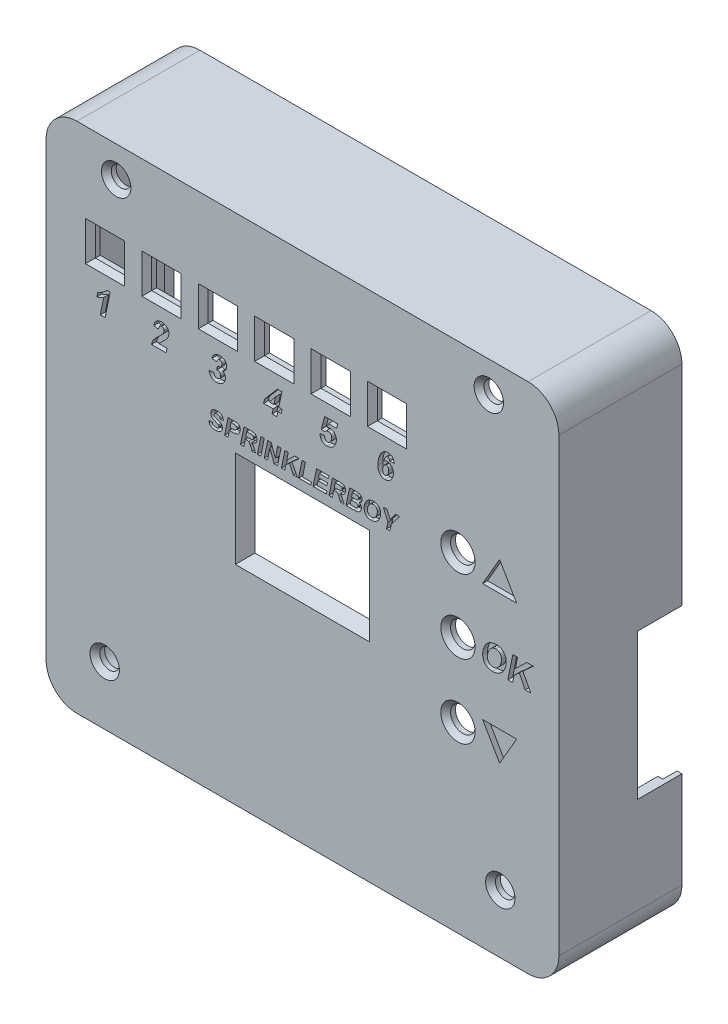
SolidWorks part; units mm, degrees
ref_plane "Front Plane" through (0, 0, 0) normal (0, 0, 1) x (1, 0, 0)
ref_plane "Top Plane" through (0, 0, 0) normal (0, 1, 0) x (1, 0, 0)
ref_plane "Right Plane" through (0, 0, 0) normal (1, 0, 0) x (0, 0, -1)
sketch "Sketch1" plane through (0, 0, 106.9354) normal (0, 0, 1) x (1, 0, 0)
  line L0 (-17.9008, 110.3032) -> (74.0994, 110.3032) construction
  line L1 (80.3867, 104.0159) -> (80.3867, 61.3601) construction
  line L2 (-24.1881, 12.0157) -> (-24.1881, 104.0159) construction
  line L3 (-13.5528, 5.7284) -> (-17.9008, 5.7284) construction
  line L6 (-17.9008, 110.3032) -> (74.0994, 110.3032)
  line L7 (80.3867, 104.0159) -> (80.3867, 61.3601)
  line L8 (-24.1881, 12.0157) -> (-24.1881, 104.0159)
  line L9 (-13.5528, 5.7284) -> (-17.9008, 5.7284)
  line L13 (80.3867, 31.6547) -> (80.3867, 12.0157) construction
  line L14 (80.3867, 31.6547) -> (80.3867, 12.0157)
  line L15 (-13.5528, 5.7284) -> (69.2377, 5.7284) construction
  line L16 (-13.5528, 5.7284) -> (69.2377, 5.7284)
  line L17 (80.3867, 31.6547) -> (80.3867, 61.3601) construction
  line L18 (80.3867, 31.6547) -> (80.3867, 61.3601)
  line L19 (74.0994, 5.7284) -> (69.2377, 5.7284) construction
  line L20 (74.0994, 5.7284) -> (69.2377, 5.7284)
  arc A0 (80.3867, 104.0159) -> (74.0994, 110.3032) centre (74.0994, 104.0159) ccw construction
  arc A1 (-17.9008, 110.3032) -> (-24.1881, 104.0159) centre (-17.9008, 104.0159) ccw construction
  arc A2 (-24.1881, 12.0157) -> (-17.9008, 5.7284) centre (-17.9008, 12.0157) ccw construction
  arc A4 (80.3867, 104.0159) -> (74.0994, 110.3032) centre (74.0994, 104.0159) ccw
  arc A5 (-17.9008, 110.3032) -> (-24.1881, 104.0159) centre (-17.9008, 104.0159) ccw
  arc A6 (-24.1881, 12.0157) -> (-17.9008, 5.7284) centre (-17.9008, 12.0157) ccw
  arc A8 (74.0994, 5.7284) -> (80.3867, 12.0157) centre (74.0994, 12.0157) ccw construction
  arc A9 (74.0994, 5.7284) -> (80.3867, 12.0157) centre (74.0994, 12.0157) ccw
extrude "Boss-Extrude1" add sketch "Sketch1" along normal blind 2
sketch "Sketch3" plane through (0, 0, 106.9354) normal (0, 0, -1) x (-1, 0, 0)
  line L13 (24.1881, 104.0159) -> (24.1881, 12.0157) construction
  line L14 (17.9008, 5.7284) -> (-74.0994, 5.7284) construction
  line L15 (-80.3867, 12.0157) -> (-80.3867, 104.0159) construction
  line L16 (-74.0994, 110.3032) -> (17.9008, 110.3032) construction
  line L17 (24.1881, 104.0159) -> (24.1881, 12.0157)
  line L18 (17.9008, 5.7284) -> (-74.0994, 5.7284)
  line L19 (-80.3867, 12.0157) -> (-80.3867, 104.0159)
  line L20 (-74.0994, 110.3032) -> (17.9008, 110.3032)
  line L21 (-74.0994, 108.3032) -> (17.9008, 108.3032)
  line L22 (22.1881, 104.0159) -> (22.1881, 12.0157)
  line L23 (17.9008, 7.7284) -> (-74.0994, 7.7284)
  line L24 (-78.3867, 12.0157) -> (-78.3867, 104.0159)
  arc A12 (24.1881, 104.0159) -> (17.9008, 110.3032) centre (17.9008, 104.0159) ccw construction
  arc A13 (17.9008, 5.7284) -> (24.1881, 12.0157) centre (17.9008, 12.0157) ccw construction
  arc A14 (-80.3867, 12.0157) -> (-74.0994, 5.7284) centre (-74.0994, 12.0157) ccw construction
  arc A15 (-74.0994, 110.3032) -> (-80.3867, 104.0159) centre (-74.0994, 104.0159) ccw construction
  arc A16 (24.1881, 104.0159) -> (17.9008, 110.3032) centre (17.9008, 104.0159) ccw
  arc A17 (17.9008, 5.7284) -> (24.1881, 12.0157) centre (17.9008, 12.0157) ccw
  arc A18 (-80.3867, 12.0157) -> (-74.0994, 5.7284) centre (-74.0994, 12.0157) ccw
  arc A19 (-74.0994, 110.3032) -> (-80.3867, 104.0159) centre (-74.0994, 104.0159) ccw
  arc A20 (22.1881, 104.0159) -> (17.9008, 108.3032) centre (17.9008, 104.0159) ccw
  arc A21 (17.9008, 7.7284) -> (22.1881, 12.0157) centre (17.9008, 12.0157) ccw
  arc A22 (-78.3867, 12.0157) -> (-74.0994, 7.7284) centre (-74.0994, 12.0157) ccw
  arc A23 (-74.0994, 108.3032) -> (-78.3867, 104.0159) centre (-74.0994, 104.0159) ccw
  dimension "D1" = 2
extrude "Boss-Extrude2" add sketch "Sketch3" along normal up to surface (20.1862 mm away)
sketch "Sketch4" plane through (0, 0, 108.9354) normal (0, 0, 1) x (1, 0, 0)
  circle A0 centre (-9.9008, 104.0159) radius 2
  circle A1 centre (66.0994, 104.0159) radius 2
  circle A2 centre (68.4425, 17.6725) radius 2
  circle A3 centre (-12.244, 17.6725) radius 1.998
extrude "Cut-Extrude1" cut sketch "Sketch4" against normal up to next
sketch "Sketch5" plane through (0, 0, 108.9354) normal (0, 0, 1) x (1, 0, 0)
  line L0 (39.2941, 65.3848) -> (16.9045, 65.3848) construction
  line L1 (16.9045, 65.3848) -> (39.2941, 65.3848)
  line L2 (16.9045, 65.3848) -> (16.9045, 50.6848)
  line L3 (16.9045, 50.6848) -> (39.2941, 50.6848)
  line L4 (39.2941, 65.3848) -> (39.2941, 50.6848)
  line L5 (16.9045, 65.3848) -> (16.9045, 50.6848) construction
  line L6 (16.9045, 50.6848) -> (39.2941, 50.6848) construction
extrude "Cut-Extrude2" cut sketch "Sketch5" against normal up to next
chamfer "Chamfer1" distance 2.5 angle 45 4 edges at (28.0993, 50.6848, 108.9354) (39.2941, 58.0348, 108.9354) (16.9045, 58.0348, 108.9354) (28.0993, 65.3848, 108.9354)
sketch "Sketch7" plane through (80.3867, 0, 0) normal (1, 0, 0) x (0, 0, -1)
  line L0 (-92.9354, 104.0159) -> (-92.9354, 12.0157) construction
  line L1 (-92.9354, 31.6547) -> (-75.9354, 31.6547)
  line L2 (-92.9354, 31.6547) -> (-92.9354, 61.3601)
  line L3 (-92.9354, 61.3601) -> (-75.9354, 61.3601)
  line L4 (-75.9354, 31.6547) -> (-75.9354, 61.3601)
  line L5 (-83.5354, 31.7547) -> (-91.3354, 31.7547) construction
  line L6 (-83.5354, 61.2601) -> (-91.3354, 61.2601) construction
  dimension "D1" = 17
  dimension "D2" = 0.1
  dimension "D3" = 0.1
extrude "Cut-Extrude4" cut sketch "Sketch7" against normal up to next
sketch "Sketch8" plane through (0, 5.7284, 0) normal (0, -1, 0) x (1, 0, 0)
  line L0 (74.0994, 86.7492) -> (-17.9008, 86.7492) construction
  line L1 (-13.5528, 86.7492) -> (51.7933, 86.7492)
  line L2 (-13.5528, 86.7492) -> (-13.5528, 90.2354)
  line L3 (-13.5528, 90.2354) -> (51.7933, 90.2354)
  line L4 (51.7933, 86.7492) -> (51.7933, 90.2354)
  line L5 (-13.5528, 83.7492) -> (-13.5528, 73.2354) construction
  line L6 (51.6933, 81.1633) -> (51.6933, 73.3354) construction
  line L7 (-13.5528, 73.2354) -> (69.2377, 73.2354) construction
  dimension "D1" = 0.1
  dimension "D2" = 17
extrude "Cut-Extrude5" cut sketch "Sketch8" against normal up to next and the other way through all
sketch "Sketch9" plane through (0, 0, 108.9354) normal (0, 0, 1) x (1, 0, 0)
  line L0 (-15.0508, 92.6158) -> (-15.0508, 87.4158) construction
  line L1 (-15.1508, 93.0158) -> (-9.1508, 93.0158)
  line L2 (-15.1508, 93.0158) -> (-15.1508, 87.0158)
  line L3 (-15.1508, 87.0158) -> (-9.1508, 87.0158)
  line L4 (-9.1508, 93.0158) -> (-9.1508, 87.0158)
  line L5 (-14.7508, 87.1158) -> (-9.5508, 87.1158) construction
  line L6 (-9.2508, 87.4158) -> (-9.2508, 92.6158) construction
  line L7 (-9.5508, 92.9158) -> (-14.7508, 92.9158) construction
  line L8 (1.9492, 92.9158) -> (-3.2508, 92.9158) construction
  line L9 (-3.6508, 93.0158) -> (2.3492, 93.0158)
  line L10 (-3.6508, 93.0158) -> (-3.6508, 87.0158)
  line L11 (-3.6508, 87.0158) -> (2.3492, 87.0158)
  line L12 (2.3492, 93.0158) -> (2.3492, 87.0158)
  line L13 (-3.5508, 92.6158) -> (-3.5508, 87.4158) construction
  line L14 (-3.2508, 87.1158) -> (1.9492, 87.1158) construction
  line L15 (2.2492, 87.4158) -> (2.2492, 92.6158) construction
  line L16 (7.9492, 92.6158) -> (7.9492, 87.4158) construction
  line L17 (7.8492, 93.0158) -> (13.8492, 93.0158)
  line L18 (7.8492, 93.0158) -> (7.8492, 87.0158)
  line L19 (7.8492, 87.0158) -> (13.8492, 87.0158)
  line L20 (13.8492, 93.0158) -> (13.8492, 87.0158)
  line L21 (13.4492, 92.9158) -> (8.2492, 92.9158) construction
  line L22 (13.7492, 87.4158) -> (13.7492, 92.6158) construction
  line L23 (8.2492, 87.1158) -> (13.4492, 87.1158) construction
  line L24 (24.9493, 92.9158) -> (19.7493, 92.9158) construction
  line L25 (19.3493, 93.0158) -> (25.3493, 93.0158)
  line L26 (19.3493, 93.0158) -> (19.3493, 87.0158)
  line L27 (19.3493, 87.0158) -> (25.3493, 87.0158)
  line L28 (25.3493, 93.0158) -> (25.3493, 87.0158)
  line L29 (19.4493, 92.6158) -> (19.4493, 87.4158) construction
  line L30 (19.7493, 87.1158) -> (24.9493, 87.1158) construction
  line L31 (25.2493, 87.4158) -> (25.2493, 92.6158) construction
  line L32 (36.4493, 92.9158) -> (31.2493, 92.9158) construction
  line L33 (30.8493, 93.0158) -> (36.8493, 93.0158)
  line L34 (30.8493, 93.0158) -> (30.8493, 87.0158)
  line L35 (30.8493, 87.0158) -> (36.8493, 87.0158)
  line L36 (36.8493, 93.0158) -> (36.8493, 87.0158)
  line L37 (42.3493, 93.0158) -> (48.3493, 93.0158)
  line L38 (42.3493, 93.0158) -> (42.3493, 87.0158)
  line L39 (42.3493, 87.0158) -> (48.3493, 87.0158)
  line L40 (48.3493, 93.0158) -> (48.3493, 87.0158)
  line L41 (36.7493, 87.4158) -> (36.7493, 92.6158) construction
  line L42 (31.2493, 87.1158) -> (36.4493, 87.1158) construction
  line L43 (30.9493, 92.6158) -> (30.9493, 87.4158) construction
  line L44 (42.4493, 92.6158) -> (42.4493, 87.4158) construction
  line L45 (42.7493, 87.1158) -> (47.9493, 87.1158) construction
  line L46 (48.2493, 87.4158) -> (48.2493, 92.6158) construction
  line L47 (47.9493, 92.9158) -> (42.7493, 92.9158) construction
  dimension "D1" = 0.1
  dimension "D2" = 0.1
  dimension "D3" = 0.1
  dimension "D4" = 0.1
  dimension "D5" = 0.1
  dimension "D6" = 0.1
  dimension "D7" = 0.1
  dimension "D8" = 0.1
  dimension "D9" = 0.1
  dimension "D10" = 0.1
  dimension "D11" = 0.1
  dimension "D12" = 0.1
  dimension "D13" = 0.1
  dimension "D14" = 0.1
  dimension "D15" = 0.1
  dimension "D16" = 0.1
  dimension "D17" = 0.1
  dimension "D18" = 0.1
  dimension "D19" = 0.1
  dimension "D20" = 0.1
  dimension "D21" = 0.1
  dimension "D22" = 0.1
  dimension "D23" = 0.1
  dimension "D24" = 0.1
extrude "Cut-Extrude6" cut sketch "Sketch9" against normal up to next
sketch "Sketch10" plane through (0, 0, 108.9354) normal (0, 0, 1) x (1, 0, 0)
  circle A0 centre (59.7974, 73.0158) radius 2.5
  circle A1 centre (59.7974, 58.0158) radius 2.5
  circle A2 centre (59.7974, 43.0157) radius 2.5
  arc A3 (62.4474, 75.2658) -> (63.6474, 75.2658) centre (63.0474, 75.2658) ccw construction
  arc A5 (57.1473, 60.2658) -> (55.9473, 60.2658) centre (56.5473, 60.2658) ccw construction
  arc A6 (62.4474, 60.2658) -> (63.6474, 60.2658) centre (63.0474, 60.2658) ccw construction
  arc A7 (57.1473, 40.7657) -> (55.9473, 40.7657) centre (56.5473, 40.7657) ccw construction
  arc A8 (63.6474, 40.7657) -> (62.4474, 40.7657) centre (63.0474, 40.7657) ccw construction
  dimension "D2" = 5
  dimension "D3" = 3.25
  dimension "D4" = 2.25
  dimension "D5" = 3.25
  dimension "D6" = 5
  dimension "D8" = 3.25
  dimension "D9" = 5
  dimension "D1" = 2.25
  dimension "D7" = 2.25
extrude "Cut-Extrude7" cut sketch "Sketch10" against normal up to next
chamfer "Chamfer2" distance 1 angle 45 3 edges at (62.2974, 43.0157, 108.9354) (62.2974, 58.0158, 108.9354) (62.2974, 73.0158, 108.9354)
chamfer "Chamfer3" distance 1 angle 45 24 edges at (48.3493, 90.0158, 108.9354) (45.3493, 93.0158, 108.9354) (42.3493, 90.0158, 108.9354) (45.3493, 87.0158, 108.9354) (33.8493, 87.0158, 108.9354) (36.8493, 90.0158, 108.9354) (33.8493, 93.0158, 108.9354) (30.8493, 90.0158, 108.9354) (25.3493, 90.0158, 108.9354) (22.3493, 93.0158, 108.9354) (19.3493, 90.0158, 108.9354) (22.3493, 87.0158, 108.9354) (10.8492, 87.0158, 108.9354) (13.8492, 90.0158, 108.9354) (10.8492, 93.0158, 108.9354) (7.8492, 90.0158, 108.9354) (2.3492, 90.0158, 108.9354) (-0.6508, 93.0158, 108.9354) (-3.6508, 90.0158, 108.9354) (-0.6508, 87.0158, 108.9354) (-12.1508, 87.0158, 108.9354) (-9.1508, 90.0158, 108.9354) (-12.1508, 93.0158, 108.9354) (-15.1508, 90.0158, 108.9354)
sketch "Sketch11" plane through (0, 0, 108.9354) normal (0, 0, 1) x (1, 0, 0)
  text T0 "OK" font "Arial" height 5
extrude "Cut-Extrude8" cut sketch "Sketch11" against normal blind 1
sketch "Sketch12" plane through (0, 0, 108.9354) normal (0, 0, 1) x (1, 0, 0)
  line L1 (68.2974, 76.0158) -> (64.8332, 70.0158)
  line L2 (64.8332, 70.0158) -> (71.7615, 70.0158)
  line L3 (71.7615, 70.0158) -> (68.2974, 76.0158)
  line L7 (68.2974, 40.0157) -> (71.7615, 46.0157)
  line L8 (71.7615, 46.0157) -> (64.8332, 46.0157)
  line L9 (64.8332, 46.0157) -> (68.2974, 40.0157)
  circle A0 centre (68.2974, 72.0158) radius 2 construction
  circle A1 centre (59.7974, 73.0158) radius 3.5 construction
  circle A2 centre (59.7974, 73.0158) radius 2.5 construction
  circle A4 centre (68.2974, 44.0157) radius 2 construction
  circle A5 centre (59.7974, 43.0157) radius 3.5 construction
  dimension "D2" = 3
  dimension "D1" = 6
  dimension "D3" = 8.5
  dimension "D4" = 6
  dimension "D5" = 3
  dimension "D6" = 8.5
extrude "Cut-Extrude9" cut sketch "Sketch12" against normal blind 1
sketch "Sketch13" plane through (0, 0, 108.9354) normal (0, 0, 1) x (1, 0, 0)
  text T0 "1" font "Arial" height 5
  text T1 "2" font "Arial" height 5
  text T2 "3" font "Arial" height 5
  text T3 "4" font "Arial" height 5
  text T4 "5" font "Arial" height 5
  text T5 "6" font "Arial" height 5
extrude "Cut-Extrude10" cut sketch "Sketch13" against normal blind 1
sketch "Sketch14" plane through (0, 0, 108.9354) normal (0, 0, 1) x (1, 0, 0)
  text T0 "SPRINKLERBOY" font "Arial" height 3.5
extrude "Cut-Extrude12" cut sketch "Sketch14" against normal blind 1
sketch "Schizzo3" plane through (0, 0, 108.9354) normal (0, 0, 1) x (1, 0, 0)
  spline S0 degree 3 poles (28.3707, 32.9624) (28.4003, 33.0508) (28.4309, 33.1328) (28.4554, 33.2167) (28.5202, 33.4376) (28.6287, 33.4812) (28.8265, 33.3629) (29.1577, 33.1648) (29.4064, 33.1809) (29.7538, 33.4451) knots 10 10 10 10 11 11 11 12 12 12 13 13 13 13
  spline S1 degree 3 poles (26.9936, 35.4214) (26.9837, 35.2643) (26.9839, 35.1121) (26.9628, 34.9628) (26.8906, 34.453) (26.9614, 34.2983) (27.4029, 34.0331) (27.4431, 34.0089) (27.487, 33.9828) (27.514, 33.9463) (27.6507, 33.7615) (27.792, 33.579) (27.9129, 33.3841) (28.0243, 33.2047) (28.1215, 33.0208) (28.3707, 32.9624) knots 5 5 5 5 6 6 6 7 7 7 8 8 8 9 9 9 10 10 10 10
  spline S2 degree 3 poles (29.7538, 33.4451) (29.6587, 33.5005) (29.5875, 33.5529) (29.5083, 33.5858) (29.3144, 33.6662) (29.1873, 33.8094) (29.1235, 34.0017) (29.0268, 34.2938) (28.8358, 34.4717) (28.5351, 34.5303) (28.2311, 34.5895) (28.0208, 34.7588) (27.865, 35.0288) (27.6895, 35.3328) (27.3113, 35.4806) (26.9936, 35.4214) knots 0 0 0 0 1 1 1 2 2 2 3 3 3 4 4 4 5 5 5 5
  spline S3 degree 3 poles (30.831, 31.2383) (30.8323, 31.2978) (30.8196, 31.3619) (30.8376, 31.4158) (30.894, 31.5846) (30.9619, 31.7496) (31.0421, 31.9596) knots 117 117 117 117 118 118 118 119 119 119 119
  spline S4 degree 3 poles (32.6948, 30.1787) (32.9278, 30.3418) (33.1268, 30.4678) (33.3111, 30.6126) (33.9753, 31.1341) (34.6377, 31.6579) (35.294, 32.1893) (35.5595, 32.4043) (35.5368, 32.4708) (35.2345, 32.6224) (34.9868, 32.7465) (34.7415, 32.882) (34.5168, 33.0428) (34.3753, 33.1441) (34.2606, 33.2919) (34.1587, 33.4363) (34.0838, 33.5424) (34.0024, 33.5842) (33.8814, 33.5706) (33.5343, 33.5316) (33.2487, 33.381) (33.0363, 33.1007) (32.9598, 32.9998) (32.895, 32.8893) (32.8122, 32.7942) (32.6712, 32.6322) (32.5268, 32.472) (32.3719, 32.3234) (32.1247, 32.0861) (31.8767, 31.8482) (31.612, 31.6312) (31.431, 31.4829) (31.2245, 31.3642) (31.0219, 31.2451) (30.9737, 31.2167) (30.8954, 31.2392) (30.831, 31.2383) knots 105 105 105 105 106 106 106 107 107 107 108 108 108 109 109 109 110 110 110 111 111 111 112 112 112 113 113 113 114 114 114 115 115 115 116 116 116 117 117 117 117
  spline S5 degree 3 poles (37.8726, 34.3603) (37.8012, 34.174) (37.7274, 34.04) (37.6995, 33.897) (37.633, 33.5555) (37.4795, 33.2818) (37.1986, 33.0664) (37.0944, 32.9864) (36.9837, 32.8424) (36.9766, 32.7216) (36.954, 32.341) (36.7284, 32.1032) (36.467, 31.8835) (35.9887, 31.4816) (35.4676, 31.1584) (34.8747, 30.938) (34.5034, 30.8) (34.1637, 30.5761) (33.8117, 30.3873) (33.5272, 30.2347) (33.2382, 30.0971) (32.9057, 30.105) (32.8479, 30.1064) (32.7911, 30.1438) (32.6948, 30.1787) knots 97 97 97 97 98 98 98 99 99 99 100 100 100 101 101 101 102 102 102 103 103 103 104 104 104 105 105 105 105
  spline S6 degree 3 poles (31.3954, 37.1477) (31.7741, 36.7468) (32.1481, 36.3525) (32.5203, 35.9566) (32.9469, 35.5029) (33.4309, 35.1296) (33.9813, 34.8319) (34.2372, 34.6935) (34.4614, 34.4905) (34.6844, 34.2987) (35.0525, 33.982) (35.4011, 33.6424) (35.7714, 33.3285) (35.9749, 33.156) (36.0519, 33.1572) (36.2299, 33.3549) (36.4941, 33.6484) (36.7256, 33.9712) (36.9797, 34.2743) (37.1593, 34.4887) (37.3469, 34.6973) (37.5427, 34.8969) (37.6919, 35.0489) (37.8383, 35.0762) (38.0153, 34.9617) (38.2891, 34.7847) (38.5633, 34.6009) (38.8059, 34.3846) (39.6068, 33.6705) (40.3977, 32.9449) (41.1839, 32.2145) (41.5158, 31.9061) (41.8292, 31.5777) (42.1448, 31.2522) (42.2505, 31.1432) (42.348, 31.0223) (42.4291, 30.894) (42.5195, 30.7511) (42.4534, 30.6351) (42.2881, 30.6449) (42.1704, 30.6518) (42.0371, 30.6677) (41.9413, 30.728) (41.3164, 31.1219) (40.6855, 31.513) (40.1911, 32.0743) (39.9962, 32.2955) (39.8402, 32.55) (39.5805, 32.7098) (39.4147, 32.8118) (39.2326, 32.9024) (39.0989, 33.0386) (38.8189, 33.3238) (38.5689, 33.6384) (38.3006, 33.9355) (38.1789, 34.0703) (38.0429, 34.1923) (37.8726, 34.3603) knots 78 78 78 78 79 79 79 80 80 80 81 81 81 82 82 82 83 83 83 84 84 84 85 85 85 86 86 86 87 87 87 88 88 88 89 89 89 90 90 90 91 91 91 92 92 92 93 93 93 94 94 94 95 95 95 96 96 96 97 97 97 97
  spline S7 degree 3 number of poles 172 (25.0103, 36.3727) -> (31.3954, 37.1477)
  spline S8 degree 3 poles (25.9032, 31.065) (25.5886, 31.2528) (25.4281, 31.6472) (25.5642, 31.9828) (25.742, 32.4214) (25.8228, 32.8688) (25.7908, 33.3403) (25.7837, 33.4437) (25.8098, 33.5495) (25.8227, 33.6539) (25.8531, 33.8991) (25.8653, 34.1486) (25.9218, 34.3876) (25.968, 34.5835) (26.0591, 34.7706) (26.1453, 34.9546) (26.2792, 35.2402) (26.2673, 35.3458) (26.0378, 35.5504) (25.7777, 35.7823) (25.5166, 36.013) (25.2516, 36.2392) (25.196, 36.2866) (25.1217, 36.3122) (25.0103, 36.3727) knots 13 13 13 13 14 14 14 15 15 15 16 16 16 17 17 17 18 18 18 19 19 19 20 20 20 21 21 21 21
  spline S9 degree 3 poles (26.223, 32.0099) (26.03, 31.8279) (25.9736, 31.6084) (26.0018, 31.3591) (26.0144, 31.2469) (26.0236, 31.1337) (25.9032, 31.065) knots 11 11 11 11 12 12 12 13 13 13 13
  spline S10 degree 3 poles (31.0421, 31.9596) (30.9082, 31.9759) (30.7944, 32.0097) (30.6851, 31.9987) (30.4678, 31.9768) (30.2632, 32.0052) (30.0704, 32.1015) (29.7739, 32.2496) (29.4735, 32.2673) (29.1711, 32.1341) (28.5234, 31.8488) (28.0101, 32.0981) (27.5349, 32.5282) (27.3394, 32.7052) (27.1395, 32.8791) (26.9285, 33.0369) (26.7405, 33.1775) (26.629, 33.1179) (26.6158, 32.8795) (26.6056, 32.6949) (26.6168, 32.5092) (26.6113, 32.3242) (26.6078, 32.2084) (26.6009, 32.0909) (26.576, 31.9785) (26.5631, 31.9204) (26.5107, 31.8312) (26.471, 31.8283) (26.4139, 31.8242) (26.3495, 31.8824) (26.2935, 31.9215) (26.265, 31.9413) (26.248, 31.9775) (26.223, 32.0099) knots 0 0 0 0 1 1 1 2 2 2 3 3 3 4 4 4 5 5 5 6 6 6 7 7 7 8 8 8 9 9 9 10 10 10 11 11 11 11
  spline S11 degree 3 poles (28.8018, 17.4103) (28.7954, 17.5593) (28.6614, 17.6925) (28.5116, 17.6867) (28.3723, 17.6813) (28.226, 17.608) (28.2541, 17.4266) knots 2 2 2 2 3 3 3 4 4 4 4
  spline S12 degree 3 poles (28.2541, 17.4266) (28.2562, 17.2617) (28.3812, 17.1212) (28.5263, 17.1206) (28.672, 17.1199) (28.8082, 17.2632) (28.8018, 17.4103) knots 0 0 0 0 1 1 1 2 2 2 2
  spline S13 degree 3 poles (22.8204, 19.942) (22.9551, 19.9451) (23.1, 20.0979) (23.0973, 20.2339) (23.0946, 20.3712) (22.9456, 20.5154) (22.808, 20.5137) knots 2 2 2 2 3 3 3 4 4 4 4
  spline S14 degree 3 poles (22.808, 20.5137) (22.6576, 20.5119) (22.5462, 20.3861) (22.5483, 20.2207) (22.5505, 20.055) (22.6644, 19.9383) (22.8204, 19.942) knots 0 0 0 0 1 1 1 2 2 2 2
  spline S15 degree 3 poles (20.613, 22.1633) (20.6143, 22.0216) (20.7553, 21.8784) (20.8941, 21.8779) (21.0477, 21.8773) (21.1819, 22.0023) (21.1848, 22.1487) knots 2 2 2 2 3 3 3 4 4 4 4
  spline S16 degree 3 poles (21.1848, 22.1487) (21.1877, 22.2941) (21.0391, 22.4515) (20.9, 22.4503) (20.7755, 22.4493) (20.6118, 22.2856) (20.613, 22.1633) knots 0 0 0 0 1 1 1 2 2 2 2
  spline S17 degree 3 poles (30.8017, 17.4972) (30.8032, 17.333) (30.9173, 17.213) (31.0734, 17.2117) (31.2166, 17.2106) (31.3422, 17.3453) (31.3441, 17.5023) (31.3459, 17.6554) (31.2189, 17.784) (31.0661, 17.7837) knots 1 1 1 1 2 2 2 3 3 3 4 4 4 4
  spline S18 degree 3 poles (31.0661, 17.7837) (30.9098, 17.7834) (30.8002, 17.6646) (30.8017, 17.4972) knots 0 0 0 0 1 1 1 1
  spline S19 degree 3 poles (25.7242, 17.5144) (25.7193, 17.3486) (25.8416, 17.2118) (25.9945, 17.2118) (26.1422, 17.2118) (26.267, 17.3403) (26.2694, 17.495) knots 2 2 2 2 3 3 3 4 4 4 4
  spline S20 degree 3 poles (26.2694, 17.495) (26.2721, 17.664) (26.1684, 17.7794) (26.009, 17.785) (25.8567, 17.7902) (25.7287, 17.6686) (25.7242, 17.5144) knots 0 0 0 0 1 1 1 2 2 2 2
  spline S21 degree 3 poles (17.7955, 23.6252) (17.9366, 23.6237) (18.0756, 23.7618) (18.0783, 23.9062) (18.0815, 24.0786) (17.9685, 24.1986) (17.8013, 24.2005) knots 2 2 2 2 3 3 3 4 4 4 4
  spline S22 degree 3 poles (17.8013, 24.2005) (17.6517, 24.2022) (17.5347, 24.0877) (17.5309, 23.936) (17.5267, 23.7705) (17.6491, 23.6268) (17.7955, 23.6252) knots 0 0 0 0 1 1 1 2 2 2 2
  spline S23 degree 3 poles (36.1356, 22.4502) (36.0133, 22.4491) (35.8552, 22.2846) (35.8535, 22.1567) (35.8516, 22.014) (35.9874, 21.8799) (36.1372, 21.8765) knots 2 2 2 2 3 3 3 4 4 4 4
  spline S24 degree 3 poles (36.1372, 21.8765) (36.2785, 21.8733) (36.4194, 22.0092) (36.4237, 22.1528) (36.4281, 22.3007) (36.2819, 22.4517) (36.1356, 22.4502) knots 0 0 0 0 1 1 1 2 2 2 2
  spline S25 degree 3 poles (39.6229, 23.9255) (39.6216, 24.0626) (39.489, 24.192) (39.3448, 24.1969) (39.1887, 24.2023) (39.0612, 24.0733) (39.0588, 23.9076) knots 2 2 2 2 3 3 3 4 4 4 4
  spline S26 degree 3 poles (39.0588, 23.9076) (39.0568, 23.7659) (39.1903, 23.6276) (39.3335, 23.6233) (39.4645, 23.6193) (39.6243, 23.7862) (39.6229, 23.9255) knots 0 0 0 0 1 1 1 2 2 2 2
  spline S27 degree 3 poles (34.264, 20.5138) (34.1348, 20.5107) (33.9378, 20.3416) (33.9415, 20.2369) (33.9459, 20.1147) (34.1348, 19.9417) (34.2644, 19.9413) knots 2 2 2 2 3 3 3 4 4 4 4
  spline S28 degree 3 poles (34.2644, 19.9413) (34.4003, 19.9409) (34.5462, 20.0833) (34.5504, 20.2205) (34.555, 20.3703) (34.4114, 20.5174) (34.264, 20.5138) knots 0 0 0 0 1 1 1 2 2 2 2
  spline S29 degree 3 poles (30.0964, 21.3289) (30.0963, 21.969) (30.098, 22.6091) (30.0958, 23.2492) (30.0948, 23.5552) (29.9275, 23.7212) (29.627, 23.7215) (28.8864, 23.7224) (28.1458, 23.7241) (27.4051, 23.7221) (27.1324, 23.7214) (26.9628, 23.5471) (26.9622, 23.2759) (26.9614, 22.8898) (26.962, 22.5036) (26.9621, 22.1174) knots 5 5 5 5 6 6 6 7 7 7 8 8 8 9 9 9 10 10 10 10
  spline S30 degree 3 poles (26.9621, 22.1174) (26.9621, 21.7417) (26.9612, 21.3661) (26.9623, 20.9905) (26.9632, 20.7074) (27.1203, 20.541) (27.3977, 20.5402) (28.1542, 20.5381) (28.9107, 20.5389) (29.6672, 20.5421) (29.9317, 20.5431) (30.0883, 20.699) (30.098, 20.9639) (30.1025, 21.0854) (30.0965, 21.2072) (30.0964, 21.3289) knots 0 0 0 0 1 1 1 2 2 2 3 3 3 4 4 4 5 5 5 5
  spline S31 degree 3 poles (31.1925, 18.134) (31.4324, 18.0711) (31.6546, 17.8443) (31.6913, 17.6133) (31.7343, 17.342) (31.6082, 17.07) (31.3781, 16.938) (31.1661, 16.8164) (30.8748, 16.8372) (30.6772, 16.988) (30.4122, 17.1904) (30.3583, 17.5677) (30.5556, 17.8504) (30.5916, 17.9019) (30.6344, 17.9487) (30.6935, 18.0218) knots 199 199 199 199 200 200 200 201 201 201 202 202 202 203 203 203 204 204 204 204
  spline S32 degree 3 poles (31.4647, 20.7845) (31.4655, 20.6593) (31.3736, 20.5919) (31.2589, 20.5841) (31.1223, 20.5749) (30.984, 20.5847) (30.8468, 20.5929) (30.6049, 20.6073) (30.5825, 20.5887) (30.5815, 20.3482) (30.5807, 20.151) (30.5422, 20.1138) (30.3358, 20.1194) (30.1943, 20.1233) (30.1016, 20.0822) (30.1, 19.9171) (30.0981, 19.7273) (30.0643, 19.5358) (30.0821, 19.3486) (30.0921, 19.243) (30.1602, 19.1291) (30.2327, 19.0455) (30.4752, 18.7661) (30.7281, 18.4954) (30.9853, 18.2295) (31.0348, 18.1783) (31.1194, 18.1532) (31.1925, 18.134) knots 190 190 190 190 191 191 191 192 192 192 193 193 193 194 194 194 195 195 195 196 196 196 197 197 197 198 198 198 199 199 199 199
  spline S33 degree 3 number of poles 94 (30.5743, 22.4263) -> (31.4647, 20.7845)
  spline S34 degree 3 number of poles 76 (31.2431, 23.569) -> (30.5743, 22.4263)
  spline S35 degree 3 poles (29.5528, 24.1641) (29.5996, 24.2155) (29.6757, 24.2612) (29.6869, 24.3194) (29.7084, 24.4317) (29.6959, 24.5511) (29.6927, 24.6674) (29.6888, 24.8052) (29.7506, 24.8994) (29.8864, 24.9104) (30.0361, 24.9225) (30.0838, 24.8125) (30.0908, 24.6841) (30.0986, 24.5416) (30.1025, 24.3988) (30.1039, 24.2562) (30.1052, 24.1266) (30.1573, 24.0656) (30.296, 24.0675) (30.5596, 24.0711) (30.5744, 24.0493) (30.5651, 23.7746) (30.5597, 23.6139) (30.6035, 23.5664) (30.7672, 23.5651) (30.9258, 23.5639) (31.0845, 23.565) (31.2431, 23.569) knots 125 125 125 125 126 126 126 127 127 127 128 128 128 129 129 129 130 130 130 131 131 131 132 132 132 133 133 133 134 134 134 134
  spline S36 degree 3 poles (28.8596, 24.148) (29.0017, 24.1446) (29.0045, 24.2574) (29.003, 24.3622) (29.0015, 24.468) (28.9962, 24.5739) (28.9985, 24.6796) (29.002, 24.8358) (29.0799, 24.9253) (29.2065, 24.9268) (29.3351, 24.9283) (29.4047, 24.8442) (29.4071, 24.68) (29.4088, 24.5583) (29.3924, 24.4338) (29.4142, 24.3161) (29.4248, 24.2589) (29.5044, 24.2144) (29.5528, 24.1641) knots 119 119 119 119 120 120 120 121 121 121 122 122 122 123 123 123 124 124 124 125 125 125 125
  spline S37 degree 3 poles (28.1782, 24.1625) (28.3086, 24.1583) (28.3262, 24.2572) (28.3275, 24.3589) (28.3289, 24.47) (28.3297, 24.5812) (28.3275, 24.6923) (28.3252, 24.8107) (28.3765, 24.885) (28.497, 24.896) (28.6296, 24.9082) (28.6941, 24.8267) (28.7056, 24.709) (28.7168, 24.5937) (28.7133, 24.4762) (28.7071, 24.3601) (28.7009, 24.244) (28.7316, 24.151) (28.8596, 24.148) knots 113 113 113 113 114 114 114 115 115 115 116 116 116 117 117 117 118 118 118 119 119 119 119
  spline S38 degree 3 number of poles 226 (26.8356, 19.07) -> (28.1782, 24.1625)
  spline S39 degree 3 poles (25.5109, 17.0952) (25.3516, 17.2988) (25.3228, 17.5273) (25.4381, 17.7621) (25.5379, 17.9652) (25.6844, 18.1111) (25.9248, 18.1474) (25.9951, 18.1581) (26.0715, 18.2084) (26.1211, 18.2626) (26.3636, 18.5277) (26.5975, 18.8008) (26.8356, 19.07) knots 34 34 34 34 35 35 35 36 36 36 37 37 37 38 38 38 38
  spline S40 degree 3 poles (26.3624, 18.0345) (26.5429, 17.8665) (26.65, 17.6729) (26.6211, 17.4221) (26.5891, 17.1443) (26.4324, 16.9725) (26.1761, 16.8855) (25.9355, 16.8038) (25.6779, 16.8818) (25.5109, 17.0952) knots 31 31 31 31 32 32 32 33 33 33 34 34 34 34
  spline S41 degree 3 poles (27.4857, 20.0978) (27.3662, 20.1023) (27.3438, 20.0094) (27.337, 19.9134) (27.3337, 19.866) (27.3234, 19.8169) (27.3316, 19.7713) (27.4169, 19.3003) (27.2425, 18.9265) (26.911, 18.6043) (26.7256, 18.424) (26.5517, 18.2319) (26.3624, 18.0345) knots 27 27 27 27 28 28 28 29 29 29 30 30 30 31 31 31 31
  spline S42 degree 3 poles (27.8482, 19.4014) (27.7298, 19.394) (27.6392, 19.4848) (27.6308, 19.6228) (27.6253, 19.7124) (27.6306, 19.8027) (27.6292, 19.8926) (27.6276, 19.993) (27.6124, 20.0931) (27.4857, 20.0978) knots 24 24 24 24 25 25 25 26 26 26 27 27 27 27
  spline S43 degree 3 poles (28.3356, 16.8124) (28.0998, 16.8814) (27.9571, 17.0557) (27.9152, 17.2994) (27.8707, 17.5579) (27.9526, 17.7757) (28.1783, 17.9136) (28.2946, 17.9848) (28.3307, 18.0672) (28.3298, 18.1956) (28.3262, 18.7406) (28.3303, 19.2856) (28.3311, 19.8306) (28.3312, 19.8781) (28.3439, 19.9355) (28.3221, 19.9708) (28.2904, 20.0223) (28.2251, 20.0981) (28.188, 20.091) (28.1331, 20.0805) (28.0605, 20.0126) (28.049, 19.9579) (28.0265, 19.8514) (28.0435, 19.737) (28.0399, 19.626) (28.0359, 19.5018) (27.9874, 19.4102) (27.8482, 19.4014) knots 15 15 15 15 16 16 16 17 17 17 18 18 18 19 19 19 20 20 20 21 21 21 22 22 22 23 23 23 24 24 24 24
  spline S44 degree 3 poles (29.0118, 19.6051) (29.0049, 19.6997) (29.0103, 19.795) (29.0075, 19.89) (29.0045, 19.9908) (28.9844, 20.0924) (28.8612, 20.097) (28.7347, 20.1017) (28.7103, 19.9988) (28.71, 19.8994) (28.7078, 19.3068) (28.7055, 18.7141) (28.7144, 18.1216) (28.7154, 18.0616) (28.7787, 17.9839) (28.8346, 17.9463) (29.1824, 17.7122) (29.2546, 17.2449) (28.979, 16.9577) (28.797, 16.768) (28.5689, 16.7442) (28.3356, 16.8124) knots 8 8 8 8 9 9 9 10 10 10 11 11 11 12 12 12 13 13 13 14 14 14 15 15 15 15
  spline S45 degree 3 poles (29.2196, 19.401) (29.0766, 19.3913) (29.0209, 19.4795) (29.0118, 19.6051) knots 7 7 7 7 8 8 8 8
  spline S46 degree 3 poles (29.4126, 19.9265) (29.3917, 19.8305) (29.4071, 19.7266) (29.4077, 19.6261) (29.4084, 19.4978) (29.3582, 19.4103) (29.2196, 19.401) knots 5 5 5 5 6 6 6 7 7 7 7
  spline S47 degree 3 poles (29.5379, 20.092) (29.4837, 20.0778) (29.4265, 19.9901) (29.4126, 19.9265) knots 4 4 4 4 5 5 5 5
  spline S48 degree 3 poles (30.6935, 18.0218) (30.4721, 18.2592) (30.2614, 18.4957) (30.0389, 18.7206) (29.8071, 18.9549) (29.6837, 19.2257) (29.6986, 19.5584) (29.7043, 19.685) (29.7002, 19.8124) (29.6929, 19.9389) (29.6874, 20.0326) (29.6366, 20.1178) (29.5379, 20.092) knots 0 0 0 0 1 1 1 2 2 2 3 3 3 4 4 4 4
  spline S49 degree 3 poles (21.5248, 26.1646) (22.0345, 26.1274) (22.5659, 26.5802) (22.502, 27.1381) knots 4 4 4 4 5 5 5 5
  spline S50 degree 3 poles (22.502, 27.1381) (22.3266, 27.1381) (22.1569, 27.1527) (21.9907, 27.1344) (21.7732, 27.1106) (21.5505, 27.0841) (21.3459, 27.0128) (21.2326, 26.9734) (21.1095, 26.8576) (21.0644, 26.7464) (20.9428, 26.4465) (21.1634, 26.191) (21.5248, 26.1646) knots 0 0 0 0 1 1 1 2 2 2 3 3 3 4 4 4 4
  spline S51 degree 3 poles (22.5043, 27.9307) (22.5531, 28.2057) (22.3386, 28.4741) (21.9804, 28.5452) (21.5637, 28.6281) (21.1755, 28.5585) (20.8132, 28.3342) (20.6307, 28.2212) (20.5462, 28.2437) (20.4189, 28.4218) (20.3392, 28.5334) (20.2576, 28.6437) (20.179, 28.756) (20.11, 28.8546) (20.1187, 28.9341) (20.2255, 29.0091) (20.9782, 29.5378) (21.7979, 29.6413) (22.6618, 29.3683) (23.2986, 29.167) (23.6604, 28.6342) (23.6605, 27.9659) (23.6607, 27.1725) (23.6576, 26.3791) (23.6632, 25.5857) (23.6643, 25.4321) (23.6209, 25.3629) (23.4576, 25.3673) (23.2146, 25.3739) (22.9712, 25.3645) (22.7279, 25.3605) (22.6016, 25.3584) (22.5444, 25.4173) (22.5493, 25.5444) (22.5535, 25.6553) (22.5501, 25.7664) (22.5501, 25.9051) knots 4 4 4 4 5 5 5 6 6 6 7 7 7 8 8 8 9 9 9 10 10 10 11 11 11 12 12 12 13 13 13 14 14 14 15 15 15 16 16 16 16
  spline S52 degree 3 poles (22.5501, 25.9051) (22.0288, 25.2356) (21.2597, 25.1911) (20.6364, 25.4043) (20.1813, 25.56) (19.9059, 25.9815) (19.8785, 26.4515) (19.8282, 27.3147) (20.4444, 27.7121) (21.0522, 27.8084) (21.5279, 27.8838) (22.0142, 27.892) (22.5043, 27.9307) knots 0 0 0 0 1 1 1 2 2 2 3 3 3 4 4 4 4
  spline S53 degree 3 poles (30.9209, 27.8862) (31.4912, 27.8862) (32.0611, 27.8862) (32.6409, 27.8862) knots 2 2 2 2 3 3 3 3
  spline S54 degree 3 poles (32.6409, 27.8862) (32.6083, 28.3419) (32.3044, 28.6071) (31.8191, 28.619) (31.3465, 28.6307) (30.9781, 28.3318) (30.9209, 27.8862) knots 0 0 0 0 1 1 1 2 2 2 2
  spline S55 degree 3 poles (29.7696, 27.636) (29.8077, 28.1304) (29.9867, 28.5691) (30.3409, 28.9219) (30.808, 29.3873) (31.3838, 29.5545) (32.0314, 29.51) (32.4876, 29.4787) (32.89, 29.3283) (33.2237, 29.0042) (33.5773, 28.6609) (33.7249, 28.2336) (33.7553, 27.7558) (33.7634, 27.6294) (33.7577, 27.5021) (33.7568, 27.3751) (33.7552, 27.1508) (33.7215, 27.1155) (33.5018, 27.1152) (32.735, 27.1141) (31.9682, 27.1142) (31.2014, 27.1139) (31.1066, 27.1139) (31.0118, 27.1139) (30.906, 27.1139) knots 8 8 8 8 9 9 9 10 10 10 11 11 11 12 12 12 13 13 13 14 14 14 15 15 15 16 16 16 16
  spline S56 degree 3 poles (30.906, 27.1139) (30.9484, 26.6154) (31.3544, 26.2513) (31.858, 26.2275) (32.2117, 26.2107) (32.521, 26.3142) (32.7972, 26.5315) (32.9479, 26.65) (33.002, 26.6441) (33.1321, 26.5078) (33.2562, 26.3778) (33.3783, 26.2457) (33.5044, 26.1177) (33.5906, 26.0302) (33.5799, 25.9587) (33.4925, 25.8767) (32.9726, 25.3894) (32.3518, 25.2238) (31.6559, 25.2929) (31.1647, 25.3417) (30.7275, 25.5106) (30.3647, 25.8575) (29.8526, 26.3471) (29.7175, 26.9611) (29.7696, 27.636) knots 0 0 0 0 1 1 1 2 2 2 3 3 3 4 4 4 5 5 5 6 6 6 7 7 7 8 8 8 8
  spline S57 degree 3 poles (39.605, 28.4512) (39.4532, 28.4512) (39.324, 28.4511) (39.1948, 28.4512) (38.7504, 28.4516) (38.3059, 28.456) (37.8616, 28.4502) (37.7105, 28.4483) (37.6528, 28.5024) (37.66, 28.6547) (37.6695, 28.8552) (37.6654, 29.0567) (37.6605, 29.2576) (37.6579, 29.3661) (37.6975, 29.4063) (37.8089, 29.4056) (38.8511, 29.3983) (39.8933, 29.3966) (40.9355, 29.39) (41.155, 29.3886) (41.1557, 29.3817) (41.1558, 29.1659) (41.1558, 29.15) (41.1558, 29.1342) (41.1558, 29.1183) (41.1552, 28.5946) (41.1508, 28.5985) (40.8043, 28.2113) (40.3004, 27.6481) (39.8034, 27.0788) (39.3041, 26.5116) (39.2664, 26.4689) (39.2333, 26.4221) (39.1729, 26.3452) knots 10 10 10 10 11 11 11 12 12 12 13 13 13 14 14 14 15 15 15 16 16 16 17 17 17 18 18 18 19 19 19 20 20 20 21 21 21 21
  spline S58 degree 3 poles (39.1729, 26.3452) (39.79, 26.3452) (40.3714, 26.3467) (40.9529, 26.3446) (41.2148, 26.3437) (41.2183, 26.337) (41.2188, 26.0808) (41.2191, 25.9168) (41.2201, 25.7528) (41.2201, 25.5888) (41.22, 25.4096) (41.1915, 25.3784) (41.0094, 25.3778) (40.6867, 25.3769) (40.364, 25.3806) (40.0413, 25.3813) (39.3271, 25.3828) (38.613, 25.3836) (37.8988, 25.3849) (37.66, 25.3854) (37.6572, 25.4139) (37.6316, 25.6453) (37.5844, 26.0717) (37.7271, 26.3897) (38.0311, 26.6973) (38.5616, 27.2343) (39.0456, 27.8173) (39.549, 28.3812) (39.5621, 28.3959) (39.5737, 28.412) (39.605, 28.4512) knots 0 0 0 0 1 1 1 2 2 2 3 3 3 4 4 4 5 5 5 6 6 6 7 7 7 8 8 8 9 9 9 10 10 10 10
  spline S59 degree 3 poles (17.5751, 25.288) (17.1011, 25.3364) (16.6741, 25.5072) (16.3255, 25.8367) (15.8745, 26.2629) (15.684, 26.8009) (15.6863, 27.4904) knots 14 14 14 14 15 15 15 16 16 16 16
  spline S60 degree 3 poles (17.2645, 26.5462) (17.6456, 26.2285) (18.1901, 26.2637) (18.5869, 26.632) (18.6256, 26.6679) (18.6628, 26.7056) (18.6993, 26.7438) (18.7819, 26.8302) (18.8616, 26.8248) (18.9438, 26.7418) (19.0964, 26.5879) (19.248, 26.4328) (19.4052, 26.2836) (19.5039, 26.1898) (19.4949, 26.0943) (19.4147, 26.0061) (18.921, 25.463) (18.3094, 25.213) (17.5751, 25.288) knots 8 8 8 8 9 9 9 10 10 10 11 11 11 12 12 12 13 13 13 14 14 14 14
  spline S61 degree 3 poles (15.6863, 27.4904) (15.6523, 28.3972) (16.3748, 29.3348) (17.4401, 29.4908) (18.1808, 29.5993) (18.8289, 29.3977) (19.3475, 28.8388) (19.5259, 28.6466) (19.5199, 28.5739) (19.3165, 28.4076) (19.1898, 28.3041) (19.058, 28.2067) (18.9333, 28.1009) (18.8106, 27.9967) (18.7119, 27.9932) (18.6002, 28.1258) (18.4515, 28.3022) (18.2618, 28.4291) (18.0335, 28.4813) (17.572, 28.5869) (17.1466, 28.3455) (16.9659, 27.8821) (16.7839, 27.4153) (16.9126, 26.8395) (17.2645, 26.5462) knots 0 0 0 0 1 1 1 2 2 2 3 3 3 4 4 4 5 5 5 6 6 6 7 7 7 8 8 8 8
  spline S62 degree 3 poles (36.8236, 25.3852) (36.6201, 25.3376) (36.4096, 25.305) (36.2008, 25.298) (35.7931, 25.2843) (35.4, 25.336) (35.086, 25.6421) (34.8733, 25.8494) (34.7759, 26.1027) (34.7743, 26.3931) (34.7707, 27.0331) (34.7732, 27.6732) (34.7732, 28.3132) (34.7732, 28.3683) (34.7732, 28.4234) (34.7732, 28.4831) knots 22 22 22 22 23 23 23 24 24 24 25 25 25 26 26 26 27 27 27 27
  spline S63 degree 3 poles (36.7828, 26.3831) (36.9106, 26.3899) (36.9838, 26.3212) (36.9878, 26.1958) (36.9945, 25.9844) (37.0052, 25.7715) (36.9856, 25.5619) (36.9795, 25.4962) (36.8903, 25.4008) (36.8236, 25.3852) knots 19 19 19 19 20 20 20 21 21 21 22 22 22 22
  spline S64 degree 3 poles (35.9478, 28.4827) (35.9478, 28.4193) (35.9478, 28.3635) (35.9478, 28.3078) (35.9479, 27.8265) (35.9565, 27.345) (35.9455, 26.8639) (35.9347, 26.3947) (36.2024, 26.2324) (36.6468, 26.3445) (36.6926, 26.3561) (36.737, 26.3807) (36.7828, 26.3831) knots 15 15 15 15 16 16 16 17 17 17 18 18 18 19 19 19 19
  spline S65 degree 3 poles (35.9478, 29.41) (36.2432, 29.41) (36.5221, 29.4051) (36.8008, 29.4121) (36.9437, 29.4157) (37.0024, 29.3672) (36.9938, 29.219) (36.9833, 29.0398) (36.9888, 28.8595) (36.9912, 28.6797) (36.993, 28.5436) (36.9418, 28.4765) (36.794, 28.4805) (36.5197, 28.488) (36.245, 28.4827) (35.9478, 28.4827) knots 10 10 10 10 11 11 11 12 12 12 13 13 13 14 14 14 15 15 15 15
  spline S66 degree 3 poles (34.7732, 29.406) (34.7732, 29.6412) (34.7731, 29.8713) (34.7733, 30.1013) (34.7735, 30.3189) (34.802, 30.3478) (35.018, 30.3481) (35.2666, 30.3485) (35.5153, 30.3445) (35.7638, 30.3496) (35.8992, 30.3524) (35.954, 30.3001) (35.9499, 30.1618) (35.9426, 29.915) (35.9478, 29.6678) (35.9478, 29.41) knots 5 5 5 5 6 6 6 7 7 7 8 8 8 9 9 9 10 10 10 10
  spline S67 degree 3 poles (34.7732, 28.4831) (34.5774, 28.4831) (34.4081, 28.4874) (34.2391, 28.4817) (34.1047, 28.4772) (34.0442, 28.5309) (34.048, 28.6679) (34.0533, 28.8582) (34.0509, 29.0487) (34.0508, 29.2391) (34.0507, 29.3566) (34.1018, 29.4119) (34.2252, 29.4075) (34.3993, 29.4014) (34.5737, 29.406) (34.7732, 29.406) knots 0 0 0 0 1 1 1 2 2 2 3 3 3 4 4 4 5 5 5 5
  spline S68 degree 3 poles (25.6935, 25.6387) (25.69, 25.3743) (25.6905, 25.3717) (25.4281, 25.3716) (25.1795, 25.3715) (24.9309, 25.3734) (24.6823, 25.3707) (24.5545, 25.3693) (24.5019, 25.43) (24.5015, 25.554) (24.4972, 26.7864) (24.4924, 28.0187) (24.4849, 29.2511) (24.4841, 29.3793) (24.5372, 29.4362) (24.6628, 29.4357) (24.9431, 29.4346) (25.2235, 29.4331) (25.5038, 29.4365) (25.6187, 29.4379) (25.669, 29.3865) (25.6685, 29.2753) (25.6677, 29.1039) (25.6683, 28.9324) (25.6683, 28.7847) knots 8 8 8 8 9 9 9 10 10 10 11 11 11 12 12 12 13 13 13 14 14 14 15 15 15 16 16 16 16
  spline S69 degree 3 poles (25.6683, 28.7847) (25.8467, 28.9484) (26.0171, 29.1267) (26.2098, 29.2763) (26.5026, 29.5036) (26.8536, 29.5157) (27.2058, 29.4938) (27.2952, 29.4882) (27.3474, 29.4395) (27.3458, 29.3381) (27.3417, 29.079) (27.3438, 28.8198) (27.3433, 28.5606) (27.3431, 28.4358) (27.2832, 28.3878) (27.156, 28.3828) (26.9411, 28.3744) (26.7215, 28.3701) (26.5136, 28.3221) (26.0818, 28.2225) (25.75, 27.842) (25.7276, 27.3982) (25.698, 26.8126) (25.7015, 26.2253) (25.6935, 25.6387) knots 0 0 0 0 1 1 1 2 2 2 3 3 3 4 4 4 5 5 5 6 6 6 7 7 7 8 8 8 8
  spline S70 degree 3 poles (27.9158, 28.2306) (27.917, 28.2306) (27.9183, 28.2306) (27.9195, 28.2306) knots 10 10 10 10 11 11 11 11
  spline S71 degree 3 poles (27.9195, 28.2306) (27.9195, 29.0976) (27.9192, 29.9646) (27.9197, 30.8317) (27.9198, 31.0285) (27.9442, 31.0535) (28.1362, 31.0543) (28.3847, 31.0553) (28.6332, 31.0549) (28.8816, 31.0545) (29.0854, 31.0542) (29.0995, 31.0406) (29.1, 30.8397) (29.1025, 29.6186) (29.1039, 28.3974) (29.1074, 27.1762) (29.1089, 26.6581) (29.1146, 26.1401) (29.1188, 25.622) (29.1203, 25.4282) (29.0925, 25.4005) (28.9018, 25.4016) (28.6375, 25.403) (28.3731, 25.4074) (28.1089, 25.4013) (27.965, 25.398) (27.9132, 25.4545) (27.9138, 25.5979) (27.9178, 26.4754) (27.9158, 27.353) (27.9158, 28.2306) knots 0 0 0 0 1 1 1 2 2 2 3 3 3 4 4 4 5 5 5 6 6 6 7 7 7 8 8 8 9 9 9 10 10 10 10
  spline S72 degree 3 poles (26.9936, 35.4214) (27.3113, 35.4806) (27.6895, 35.3328) (27.865, 35.0288) (28.0208, 34.7588) (28.2311, 34.5895) (28.5351, 34.5303) (28.8358, 34.4717) (29.0268, 34.2938) (29.1235, 34.0017) (29.1873, 33.8094) (29.3144, 33.6662) (29.5083, 33.5858) (29.5875, 33.5529) (29.6587, 33.5005) (29.7538, 33.4451) knots 8 8 8 8 9 9 9 10 10 10 11 11 11 12 12 12 13 13 13 13
  spline S73 degree 3 poles (28.3707, 32.9624) (28.1215, 33.0208) (28.0243, 33.2047) (27.9129, 33.3841) (27.792, 33.579) (27.6507, 33.7615) (27.514, 33.9463) (27.487, 33.9828) (27.4431, 34.0089) (27.4029, 34.0331) (26.9614, 34.2983) (26.8906, 34.453) (26.9628, 34.9628) (26.9839, 35.1121) (26.9837, 35.2643) (26.9936, 35.4214) knots 3 3 3 3 4 4 4 5 5 5 6 6 6 7 7 7 8 8 8 8
  spline S74 degree 3 poles (29.7538, 33.4451) (29.4064, 33.1809) (29.1577, 33.1648) (28.8265, 33.3629) (28.6287, 33.4812) (28.5202, 33.4376) (28.4554, 33.2167) (28.4309, 33.1328) (28.4003, 33.0508) (28.3707, 32.9624) knots 0 0 0 0 1 1 1 2 2 2 3 3 3 3
  spline S75 degree 3 poles (27.3439, 21.2038) (27.3441, 21.0138) (27.4168, 20.9324) (27.6095, 20.931) (28.2222, 20.9268) (28.8351, 20.9262) (29.4478, 20.9296) (29.6325, 20.9307) (29.6943, 21) (29.6953, 21.1819) (29.697, 21.4936) (29.6958, 21.8053) (29.6954, 22.117) knots 5 5 5 5 6 6 6 7 7 7 8 8 8 9 9 9 9
  spline S76 degree 3 poles (29.6954, 22.117) (29.6954, 22.4234) (29.6964, 22.7298) (29.6951, 23.0362) (29.694, 23.2688) (29.6489, 23.3187) (29.4209, 23.3197) (28.8186, 23.3224) (28.2164, 23.3221) (27.6142, 23.3202) (27.4064, 23.3195) (27.3441, 23.2529) (27.3439, 23.0422) (27.3432, 22.4294) (27.3433, 21.8166) (27.3439, 21.2038) knots 0 0 0 0 1 1 1 2 2 2 3 3 3 4 4 4 5 5 5 5
  spline S77 degree 3 poles (30.0964, 21.3289) (30.0965, 21.2072) (30.1025, 21.0854) (30.098, 20.9639) (30.0883, 20.699) (29.9317, 20.5431) (29.6672, 20.5421) (28.9107, 20.5389) (28.1542, 20.5381) (27.3977, 20.5402) (27.1203, 20.541) (26.9632, 20.7074) (26.9623, 20.9905) (26.9612, 21.3661) (26.9621, 21.7417) (26.962, 22.1174) knots 5 5 5 5 6 6 6 7 7 7 8 8 8 9 9 9 10 10 10 10
  spline S78 degree 3 poles (26.962, 22.1174) (26.962, 22.5036) (26.9614, 22.8898) (26.9622, 23.2759) (26.9628, 23.5471) (27.1324, 23.7214) (27.4051, 23.7221) (28.1458, 23.7241) (28.8864, 23.7224) (29.627, 23.7215) (29.9275, 23.7212) (30.0948, 23.5552) (30.0958, 23.2492) (30.098, 22.6091) (30.0963, 21.969) (30.0964, 21.3289) knots 0 0 0 0 1 1 1 2 2 2 3 3 3 4 4 4 5 5 5 5
  spline S79 degree 3 poles (34.264, 20.5138) (34.4114, 20.5174) (34.555, 20.3703) (34.5504, 20.2205) (34.5462, 20.0833) (34.4003, 19.9409) (34.2644, 19.9413) knots 2 2 2 2 3 3 3 4 4 4 4
  spline S80 degree 3 poles (34.2644, 19.9413) (34.1348, 19.9417) (33.9459, 20.1147) (33.9415, 20.2369) (33.9378, 20.3416) (34.1348, 20.5107) (34.264, 20.5138) knots 0 0 0 0 1 1 1 2 2 2 2
  spline S81 degree 3 poles (39.6229, 23.9255) (39.6243, 23.7862) (39.4645, 23.6193) (39.3335, 23.6233) (39.1903, 23.6276) (39.0568, 23.7659) (39.0588, 23.9076) knots 2 2 2 2 3 3 3 4 4 4 4
  spline S82 degree 3 poles (39.0588, 23.9076) (39.0612, 24.0733) (39.1887, 24.2023) (39.3448, 24.1969) (39.489, 24.192) (39.6216, 24.0626) (39.6229, 23.9255) knots 0 0 0 0 1 1 1 2 2 2 2
  spline S83 degree 3 poles (36.1356, 22.4502) (36.2819, 22.4517) (36.4281, 22.3007) (36.4237, 22.1528) (36.4194, 22.0092) (36.2785, 21.8733) (36.1372, 21.8765) knots 2 2 2 2 3 3 3 4 4 4 4
  spline S84 degree 3 poles (36.1372, 21.8765) (35.9874, 21.8799) (35.8516, 22.014) (35.8535, 22.1567) (35.8552, 22.2846) (36.0133, 22.4491) (36.1356, 22.4502) knots 0 0 0 0 1 1 1 2 2 2 2
  spline S85 degree 3 poles (17.7955, 23.6252) (17.6491, 23.6268) (17.5267, 23.7705) (17.5309, 23.936) (17.5347, 24.0877) (17.6517, 24.2022) (17.8013, 24.2005) knots 2 2 2 2 3 3 3 4 4 4 4
  spline S86 degree 3 poles (17.8013, 24.2005) (17.9685, 24.1986) (18.0815, 24.0786) (18.0783, 23.9062) (18.0756, 23.7618) (17.9366, 23.6237) (17.7955, 23.6252) knots 0 0 0 0 1 1 1 2 2 2 2
  spline S87 degree 3 poles (25.7242, 17.5144) (25.7287, 17.6686) (25.8567, 17.7902) (26.009, 17.785) (26.1684, 17.7794) (26.2721, 17.664) (26.2694, 17.495) knots 2 2 2 2 3 3 3 4 4 4 4
  spline S88 degree 3 poles (26.2694, 17.495) (26.267, 17.3403) (26.1422, 17.2118) (25.9945, 17.2118) (25.8416, 17.2118) (25.7193, 17.3486) (25.7242, 17.5144) knots 0 0 0 0 1 1 1 2 2 2 2
  spline S89 degree 3 poles (30.8017, 17.4972) (30.8002, 17.6646) (30.9098, 17.7834) (31.0661, 17.7837) knots 3 3 3 3 4 4 4 4
  spline S90 degree 3 poles (31.0661, 17.7837) (31.2189, 17.784) (31.3459, 17.6554) (31.3441, 17.5023) (31.3422, 17.3453) (31.2166, 17.2106) (31.0734, 17.2117) (30.9173, 17.213) (30.8032, 17.333) (30.8017, 17.4972) knots 0 0 0 0 1 1 1 2 2 2 3 3 3 3
  spline S91 degree 3 poles (20.613, 22.1633) (20.6118, 22.2856) (20.7755, 22.4493) (20.9, 22.4503) (21.0391, 22.4515) (21.1877, 22.2941) (21.1848, 22.1487) knots 2 2 2 2 3 3 3 4 4 4 4
  spline S92 degree 3 poles (21.1848, 22.1487) (21.1819, 22.0023) (21.0477, 21.8773) (20.8941, 21.8779) (20.7553, 21.8784) (20.6143, 22.0216) (20.613, 22.1633) knots 0 0 0 0 1 1 1 2 2 2 2
  spline S93 degree 3 poles (22.8204, 19.942) (22.6644, 19.9383) (22.5505, 20.055) (22.5483, 20.2207) (22.5462, 20.3861) (22.6576, 20.5119) (22.808, 20.5137) knots 2 2 2 2 3 3 3 4 4 4 4
  spline S94 degree 3 poles (22.808, 20.5137) (22.9456, 20.5154) (23.0946, 20.3712) (23.0973, 20.2339) (23.1, 20.0979) (22.9551, 19.9451) (22.8204, 19.942) knots 0 0 0 0 1 1 1 2 2 2 2
  spline S95 degree 3 poles (28.8018, 17.4103) (28.8082, 17.2632) (28.672, 17.1199) (28.5263, 17.1206) (28.3812, 17.1212) (28.2562, 17.2617) (28.2541, 17.4266) knots 2 2 2 2 3 3 3 4 4 4 4
  spline S96 degree 3 poles (28.2541, 17.4266) (28.226, 17.608) (28.3723, 17.6813) (28.5116, 17.6867) (28.6614, 17.6925) (28.7954, 17.5593) (28.8018, 17.4103) knots 0 0 0 0 1 1 1 2 2 2 2
  spline S97 degree 3 poles (21.5248, 26.1646) (21.1634, 26.191) (20.9428, 26.4465) (21.0644, 26.7464) (21.1095, 26.8576) (21.2326, 26.9734) (21.3459, 27.0128) (21.5505, 27.0841) (21.7732, 27.1106) (21.9907, 27.1344) (22.1569, 27.1527) (22.3266, 27.1381) (22.502, 27.1381) knots 1 1 1 1 2 2 2 3 3 3 4 4 4 5 5 5 5
  spline S98 degree 3 poles (22.502, 27.1381) (22.5659, 26.5802) (22.0345, 26.1274) (21.5248, 26.1646) knots 0 0 0 0 1 1 1 1
  spline S99 degree 3 poles (30.9209, 27.8862) (30.9781, 28.3318) (31.3465, 28.6307) (31.8191, 28.619) (32.3044, 28.6071) (32.6083, 28.3419) (32.6409, 27.8862) knots 1 1 1 1 2 2 2 3 3 3 3
  spline S100 degree 3 poles (32.6409, 27.8862) (32.0611, 27.8862) (31.4912, 27.8862) (30.9209, 27.8862) knots 0 0 0 0 1 1 1 1
  spline S101 degree 3 poles (27.3439, 23.0422) (27.3441, 23.2529) (27.4064, 23.3195) (27.6142, 23.3202) (28.2164, 23.3221) (28.8186, 23.3224) (29.4209, 23.3197) (29.6489, 23.3187) (29.694, 23.2688) (29.6951, 23.0362) (29.6964, 22.7298) (29.6954, 22.4234) (29.6958, 22.117) knots 5 5 5 5 6 6 6 7 7 7 8 8 8 9 9 9 9
  spline S102 degree 3 poles (29.6958, 22.117) (29.6958, 21.8053) (29.697, 21.4936) (29.6953, 21.1819) (29.6943, 21) (29.6325, 20.9307) (29.4478, 20.9296) (28.8351, 20.9262) (28.2222, 20.9268) (27.6095, 20.931) (27.4168, 20.9324) (27.3441, 21.0138) (27.3439, 21.2038) (27.3433, 21.8166) (27.3432, 22.4294) (27.3439, 23.0422) knots 0 0 0 0 1 1 1 2 2 2 3 3 3 4 4 4 5 5 5 5
chamfer "Chamfer4" distance 1 angle 45 4 edges at (-7.9008, 104.0159, 108.9354) (68.0994, 104.0159, 108.9354) (70.4425, 17.6725, 108.9354) (-10.246, 17.6725, 108.9354)
sketch "Sketch15" plane through (0, 0, 86.7492) normal (0, 0, -1) x (-1, 0, 0)
  line L0 (17.9008, 110.3032) -> (-74.0994, 110.3032) construction
  line L2 (24.1881, 12.0157) -> (24.1881, 104.0159) construction
  line L6 (13.5528, 5.7284) -> (17.9008, 5.7284) construction
  line L9 (-74.0994, 5.7284) -> (-51.7933, 5.7284) construction
  line L17 (-80.3867, 31.6547) -> (-80.3867, 12.0157) construction
  line L22 (-80.3867, 104.0159) -> (-80.3867, 61.3601) construction
  line L46 (-80.3867, 104.0159) -> (-80.3867, 61.3601)
  line L47 (-80.3867, 31.6547) -> (-80.3867, 12.0157)
  line L48 (-74.0994, 5.7284) -> (-51.7933, 5.7284)
  line L49 (13.5528, 5.7284) -> (17.9008, 5.7284)
  line L50 (24.1881, 12.0157) -> (24.1881, 104.0159)
  line L51 (17.9008, 110.3032) -> (-74.0994, 110.3032)
  line L52 (13.5528, 6.7284) -> (17.9008, 6.7284)
  line L53 (23.1881, 12.0157) -> (23.1881, 104.0159)
  line L54 (17.9008, 109.3032) -> (-74.0994, 109.3032)
  line L55 (-79.3867, 104.0159) -> (-79.3867, 61.3601)
  line L56 (-79.3867, 61.3601) -> (-80.3867, 61.3601)
  line L57 (13.5528, 5.7284) -> (13.5528, 6.7284)
  line L58 (-79.3867, 31.6547) -> (-79.3867, 12.0157)
  line L59 (-74.0994, 6.7284) -> (-51.7933, 6.7284)
  line L60 (-80.3867, 31.6547) -> (-79.3867, 31.6547)
  line L61 (-51.7933, 6.7284) -> (-51.7933, 5.7284)
  arc A0 (-74.0994, 110.3032) -> (-80.3867, 104.0159) centre (-74.0994, 104.0159) ccw construction
  arc A2 (24.1881, 104.0159) -> (17.9008, 110.3032) centre (17.9008, 104.0159) ccw construction
  arc A6 (17.9008, 5.7284) -> (24.1881, 12.0157) centre (17.9008, 12.0157) ccw construction
  arc A15 (-80.3867, 12.0157) -> (-74.0994, 5.7284) centre (-74.0994, 12.0157) ccw construction
  arc A39 (-80.3867, 12.0157) -> (-74.0994, 5.7284) centre (-74.0994, 12.0157) ccw
  arc A40 (17.9008, 5.7284) -> (24.1881, 12.0157) centre (17.9008, 12.0157) ccw
  arc A41 (24.1881, 104.0159) -> (17.9008, 110.3032) centre (17.9008, 104.0159) ccw
  arc A42 (-74.0994, 110.3032) -> (-80.3867, 104.0159) centre (-74.0994, 104.0159) ccw
  arc A43 (17.9008, 6.7284) -> (23.1881, 12.0157) centre (17.9008, 12.0157) ccw
  arc A44 (23.1881, 104.0159) -> (17.9008, 109.3032) centre (17.9008, 104.0159) ccw
  arc A45 (-74.0994, 109.3032) -> (-79.3867, 104.0159) centre (-74.0994, 104.0159) ccw
  arc A46 (-79.3867, 12.0157) -> (-74.0994, 6.7284) centre (-74.0994, 12.0157) ccw
  dimension "D1" = 1
  dimension "D2" = 1
extrude "Boss-Extrude3" add sketch "Sketch15" along normal blind 2.9
sketch "Sketch16" plane through (0, 5.7284, 0) normal (0, -1, 0) x (1, 0, 0)
  line L1 (69.2377, 83.8492) -> (51.7933, 83.8492)
  line L3 (69.2377, 86.7492) -> (51.7933, 86.7492)
  line L4 (51.7933, 83.8492) -> (51.7933, 86.7492)
  line L6 (69.2377, 83.8492) -> (69.2377, 86.7492)
  line L7 (69.2377, 86.7492) -> (69.2377, 83.7492) construction
extrude "Cut-Extrude13" cut sketch "Sketch16" against normal up to next
